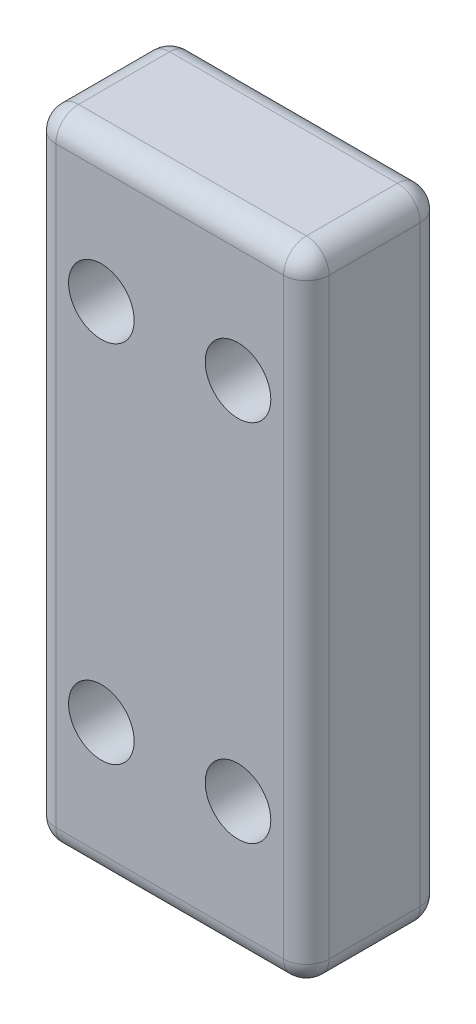
SolidWorks part; units mm, degrees
ref_plane "Front Plane" through (0, 0, 0) normal (0, 0, 1) x (1, 0, 0)
ref_plane "Top Plane" through (0, 0, 0) normal (0, 1, 0) x (1, 0, 0)
ref_plane "Right Plane" through (0, 0, 0) normal (1, 0, 0) x (0, 0, -1)
sketch "Sketch1" plane through (0, 0, 0) normal (0, 0, 1) x (1, 0, 0)
  line L1 (0, 0) -> (19.05, 0)
  line L2 (0, 0) -> (0, 44.45)
  line L3 (0, 44.45) -> (19.05, 44.45)
  line L4 (19.05, 0) -> (19.05, 44.45)
  dimension "D1" = 44.45
  dimension "D2" = 19.05
extrude "Boss-Extrude1" add sketch "Sketch1" along normal blind 9.525
sketch "Sketch2" plane through (0, 0, 9.525) normal (0, 0, 1) x (1, 0, 0)
  line L0 (4.7625, 34.925) -> (0, 34.925) construction
  line L1 (0, 44.45) -> (0, 0) construction
  line L2 (4.7625, 34.925) -> (4.7625, 44.45) construction
  line L3 (19.05, 44.45) -> (0, 44.45) construction
  line L4 (14.2875, 9.525) -> (14.2875, 0) construction
  line L5 (0, 0) -> (19.05, 0) construction
  line L6 (14.2875, 9.525) -> (19.05, 9.525) construction
  line L7 (19.05, 0) -> (19.05, 44.45) construction
  circle A0 centre (4.7625, 34.925) radius 2.286
  circle A1 centre (14.2875, 34.925) radius 2.286
  circle A2 centre (4.7625, 9.525) radius 2.286
  circle A3 centre (14.2875, 9.525) radius 2.286
  point P8 (14.6697, 5.7428)
  point P21 (0, 0)
  point P22 (0, 0)
  point P23 (0, 0)
  point P24 (0, 0)
  point P27 (11.2399, 19.8432)
  dimension "D1" = 4.572
  dimension "D2" = 9.525
  dimension "D3" = 25.4
extrude "Cut-Extrude1" cut sketch "Sketch2" against normal through all
fillet "Fillet1" radius 1.5875 12 edges at (0, 22.225, 9.525) (0, 22.225, 0) (0, 0, 4.7625) (9.525, 0, 9.525) (9.525, 0, 0) (19.05, 0, 4.7625) (19.05, 22.225, 9.525) (19.05, 22.225, 0) (19.05, 44.45, 4.7625) (9.525, 44.45, 9.525) (0, 44.45, 4.7625) (9.525, 44.45, 0)
